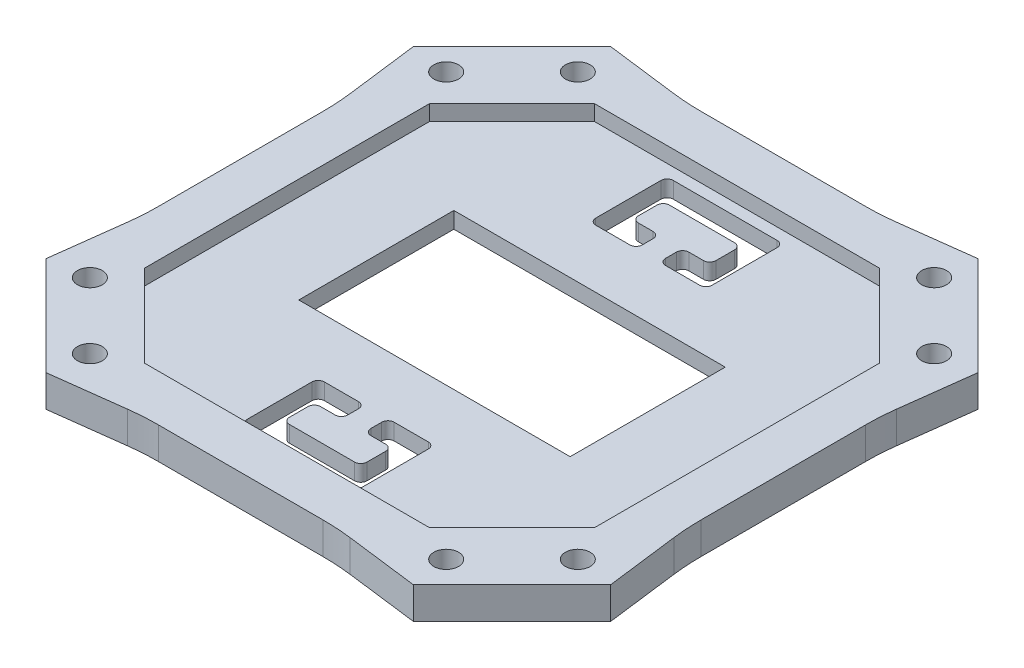
SolidWorks part; units mm, degrees
ref_plane "Front Plane" through (0, 0, 0) normal (0, 0, 1) x (1, 0, 0)
ref_plane "Top Plane" through (0, 0, 0) normal (0, 1, 0) x (1, 0, 0)
ref_plane "Right Plane" through (0, 0, 0) normal (1, 0, 0) x (0, 0, -1)
sketch "Sketch1" plane through (0, 0, 0) normal (0, 1, 0) x (1, 0, 0)
  line L0 (0, 0) -> (84.8528, 84.8528) construction
  line L1 (-35, 35) -> (35, 35) construction
  line L2 (-35, 35) -> (-35, -35) construction
  line L3 (-35, -35) -> (35, -35) construction
  line L4 (35, 35) -> (35, -35) construction
  line L5 (-35, 35) -> (35, -35) construction
  line L6 (-35, -35) -> (35, 35) construction
  line L7 (0, 35) -> (0, -35) construction
  line L8 (-12.5, 35) -> (12.5, 35)
  line L9 (35, 12.5) -> (35, -12.5)
  line L10 (12.5, -35) -> (-12.5, -35)
  line L11 (-35, -12.5) -> (-35, 12.5)
  line L12 (20.8564, 33.5843) -> (33.5843, 20.8564) construction
  line L13 (23.6848, 36.4127) -> (36.4127, 23.6848)
  line L14 (12.5, 35) -> (23.6848, 36.4127)
  line L15 (35, 12.5) -> (36.4127, 23.6848)
  line L16 (35, -12.5) -> (36.4127, -23.6848)
  line L17 (36.4127, -23.6848) -> (23.6848, -36.4127)
  line L18 (12.5, -35) -> (23.6848, -36.4127)
  line L19 (-12.5, -35) -> (-23.6848, -36.4127)
  line L20 (-23.6848, -36.4127) -> (-36.4127, -23.6848)
  line L21 (-35, -12.5) -> (-36.4127, -23.6848)
  line L22 (-35, 12.5) -> (-36.4127, 23.6848)
  line L23 (-36.4127, 23.6848) -> (-23.6848, 36.4127)
  line L24 (-12.5, 35) -> (-23.6848, 36.4127)
  circle A0 centre (22.9777, 31.463) radius 1.6
  circle A1 centre (31.463, 22.9777) radius 1.6
  circle A2 centre (31.463, -22.9777) radius 1.6
  circle A3 centre (22.9777, -31.463) radius 1.6
  circle A4 centre (-22.9777, -31.463) radius 1.6
  circle A5 centre (-31.463, -22.9777) radius 1.6
  circle A6 centre (-31.463, 22.9777) radius 1.6
  circle A7 centre (-22.9777, 31.463) radius 1.6
  point P0 (0, 0)
  point P21 (0, 0)
  point P54 (0, 0)
  dimension "D13" = 3.2
  dimension "D14" = 3.2
  dimension "D1" = 70
  dimension "D2" = 70
  dimension "D3" = 120
  dimension "D4" = 25
  dimension "D5" = 12.5
  dimension "D7" = 18
  dimension "D8" = 9
  dimension "D9" = 82
  dimension "D10" = 4
  dimension "D11" = 18
  dimension "D12" = 9
  dimension "D15" = 6
  dimension "D16" = 6
  dimension "D6" = 4
  dimension "D17" = 4
extrude "Boss-Extrude1" add sketch "Sketch1" along normal blind 4.1
sketch "Sketch2" plane through (0, 4.1, 0) normal (0, 1, 0) x (1, 0, 0)
  line L0 (0, 35) -> (0, 0)
  line L1 (12.5, 35) -> (-12.5, 35) construction
  line L2 (0, 0) -> (-35, 0)
  line L3 (-35, 12.5) -> (-35, -12.5) construction
  line L4 (-18.3696, 29) -> (18.3696, 29)
  line L5 (-4.7606, 29) -> (0, 29)
  line L6 (18.3696, 29) -> (29, 18.3696)
  line L7 (29, 18.3696) -> (29, -18.3696)
  line L8 (29, -18.3696) -> (18.3696, -29)
  line L9 (18.3696, -29) -> (-18.3696, -29)
  line L10 (-18.3696, -29) -> (-29, -18.3696)
  line L11 (-29, -18.3696) -> (-29, 18.3696)
  line L12 (-29, 18.3696) -> (-18.3696, 29)
  line L13 (-36.4127, -23.6848) -> (-23.6848, -36.4127) construction
  line L15 (-12.5, -35) -> (12.5, -35) construction
  line L16 (23.6848, -36.4127) -> (36.4127, -23.6848) construction
  line L17 (-23.6848, 36.4127) -> (-36.4127, 23.6848) construction
  line L18 (36.4127, 23.6848) -> (23.6848, 36.4127) construction
  line L19 (35, -12.5) -> (35, 12.5) construction
  dimension "D1" = 6
  dimension "D2" = 9
  dimension "D3" = 6
  dimension "D4" = 9
  dimension "D5" = 6
extrude "Cut-Extrude1" cut sketch "Sketch2" against normal blind 2 contours L12 L11 L2 L0 L4 | L11 L10 L9 L8 L7 L6 L4 L0 L2 region at (4.5703, 4.1, 4.5703) region at (-13.7109, 4.1, -13.7109)
sketch "Sketch3" plane through (0, 2.1, 0) normal (0, 1, 0) x (1, 0, 0)
  line L0 (0, 29) -> (0, 0) construction
  line L1 (-18.3696, 29) -> (18.3696, 29) construction
  line L2 (0, 0) -> (-29, 0) construction
  line L3 (-29, -18.3696) -> (-29, 18.3696) construction
  line L4 (-15, 4.6474) -> (-15, -4.6474)
  line L5 (-16.0136, -6.8956) -> (-24.0136, -13.964)
  line L6 (-29, -11.7158) -> (-29, 11.7158)
  line L7 (-24.0136, 13.964) -> (-16.0136, 6.8956)
  line L8 (-11.7158, 29) -> (11.7158, 29)
  line L9 (-6.8956, 16.0136) -> (-13.964, 24.0136)
  line L10 (4.6474, 15) -> (-4.6474, 15)
  line L11 (13.964, 24.0136) -> (6.8956, 16.0136)
  line L12 (29, 11.7158) -> (29, -11.7158)
  line L13 (16.0136, 6.8956) -> (24.0136, 13.964)
  line L14 (15, -4.6474) -> (15, 4.6474)
  line L15 (24.0136, -13.964) -> (16.0136, -6.8956)
  line L16 (11.7158, -29) -> (-11.7158, -29)
  line L17 (6.8956, -16.0136) -> (13.964, -24.0136)
  line L18 (-4.6474, -15) -> (4.6474, -15)
  line L19 (-13.964, -24.0136) -> (-6.8956, -16.0136)
  arc A0 (-15, 4.6474) -> (-16.0136, 6.8956) centre (-18, 4.6474) ccw
  arc A1 (-15, -4.6474) -> (-16.0136, -6.8956) centre (-18, -4.6474) cw
  arc A2 (-24.0136, -13.964) -> (-29, -11.7158) centre (-26, -11.7158) cw
  arc A3 (-29, 11.7158) -> (-24.0136, 13.964) centre (-26, 11.7158) cw
  arc A4 (11.7158, 29) -> (13.964, 24.0136) centre (11.7158, 26) cw
  arc A5 (-13.964, 24.0136) -> (-11.7158, 29) centre (-11.7158, 26) cw
  arc A6 (-4.6474, 15) -> (-6.8956, 16.0136) centre (-4.6474, 18) cw
  arc A7 (4.6474, 15) -> (6.8956, 16.0136) centre (4.6474, 18) ccw
  arc A8 (29, -11.7158) -> (24.0136, -13.964) centre (26, -11.7158) cw
  arc A9 (24.0136, 13.964) -> (29, 11.7158) centre (26, 11.7158) cw
  arc A10 (15, 4.6474) -> (16.0136, 6.8956) centre (18, 4.6474) cw
  arc A11 (15, -4.6474) -> (16.0136, -6.8956) centre (18, -4.6474) ccw
  arc A12 (-11.7158, -29) -> (-13.964, -24.0136) centre (-11.7158, -26) cw
  arc A13 (13.964, -24.0136) -> (11.7158, -29) centre (11.7158, -26) cw
  arc A14 (4.6474, -15) -> (6.8956, -16.0136) centre (4.6474, -18) cw
  arc A15 (-4.6474, -15) -> (-6.8956, -16.0136) centre (-4.6474, -18) ccw
  point P18 (-15, 6)
  point P21 (-15, -6)
  point P24 (-29, -18.3696)
  point P27 (-29, 18.3696)
  point P65 (0, 0)
  dimension "D3" = 3
  dimension "D1" = 15
  dimension "D2" = 12
  dimension "D4" = 4
extrude "Cut-Extrude2" [suppressed] cut sketch "Sketch3" against normal blind 1.5
sketch "Sketch4" plane through (0, 2.1, 0) normal (0, 1, 0) x (1, 0, 0)
  line L1 (0, 0) -> (15.25, 0) construction
  line L2 (0, 0) -> (0, 15.25) construction
  line L3 (0, 15.25) -> (15.25, 15.25) construction
  line L4 (15.25, 0) -> (15.25, 15.25) construction
  circle A0 centre (15.25, 15.25) radius 1.5
  dimension "D2" = 3
  dimension "D1" = 15.25
extrude "Cut-Extrude3" [suppressed] cut sketch "Sketch4" against normal through all
sketch "Sketch5" [suppressed] plane through (0, 2, 0) normal (0, 1, 0) x (1, 0, 0)
  circle A0 centre (15.25, 15.25) radius 4
  circle A1 centre (15.25, 15.25) radius 1.5 construction
  circle A2 centre (15.25, 15.25) radius 1.5
  dimension "D1" = 8
extrude "Boss-Extrude3" [suppressed] add sketch "Sketch5" along normal blind 1.5
ref_axis "Axis1" through (0, 4.2, 0) along (0, -1, 0)
pattern_circular "CirPattern1" [suppressed] count 4 over 360 about axis through (0, 4.2, 0) along (0, -1, 0) of bodies 106
fillet "Fillet1" [suppressed] radius 2
fillet "Fillet2" radius 30 8 edges at (-35, 2.05, 12.5) (-35, 2.05, -12.5) (-12.5, 2.05, -35) (12.5, 2.05, -35) (35, 2.05, -12.5) (35, 2.05, 12.5) (12.5, 2.05, 35) (-12.5, 2.05, 35)
sketch "Sketch6" plane through (0, 2.1, 0) normal (0, 1, 0) x (1, 0, 0)
  line L0 (0, 0) -> (0, 24.5268) construction
  line L1 (0, 0) -> (-22.3432, 0) construction
  line L2 (-1.5, 19.7) -> (-1.5, 18.3)
  line L3 (-6.7, 27.5) -> (6.7, 27.5)
  line L4 (-7.5, 26.7) -> (-7.5, 18.3)
  line L5 (-6.7, 17.5) -> (-2.3, 17.5)
  line L6 (7.5, 26.7) -> (7.5, 18.3)
  line L7 (-7.5, 27.5) -> (7.5, 17.5) construction
  line L8 (-7.5, 17.5) -> (7.5, 27.5) construction
  line L9 (-4.2, 24.5) -> (4.2, 24.5)
  line L10 (-5, 23.7) -> (-5, 21.3)
  line L11 (-4.2, 20.5) -> (-2.3, 20.5)
  line L12 (5, 23.7) -> (5, 21.3)
  line L13 (-5, 24.5) -> (5, 20.5) construction
  line L14 (-5, 20.5) -> (5, 24.5) construction
  line L15 (1.5, 19.7) -> (1.5, 18.3)
  line L16 (2.3, 20.5) -> (4.2, 20.5)
  line L17 (2.3, 17.5) -> (6.7, 17.5)
  line L18 (-1.5, -19.7) -> (-1.5, -18.3)
  line L19 (-4.2, -20.5) -> (-2.3, -20.5)
  line L20 (-5, -23.7) -> (-5, -21.3)
  line L21 (-4.2, -24.5) -> (4.2, -24.5)
  line L22 (5, -23.7) -> (5, -21.3)
  line L23 (2.3, -20.5) -> (4.2, -20.5)
  line L24 (1.5, -19.7) -> (1.5, -18.3)
  line L25 (2.3, -17.5) -> (6.7, -17.5)
  line L26 (7.5, -26.7) -> (7.5, -18.3)
  line L27 (-6.7, -27.5) -> (6.7, -27.5)
  line L28 (-7.5, -26.7) -> (-7.5, -18.3)
  line L29 (-6.7, -17.5) -> (-2.3, -17.5)
  arc A0 (-7.5, 18.3) -> (-6.7, 17.5) centre (-6.7, 18.3) ccw
  arc A1 (1.5, 19.7) -> (2.3, 20.5) centre (2.3, 19.7) cw
  arc A2 (-1.5, 19.7) -> (-2.3, 20.5) centre (-2.3, 19.7) ccw
  arc A3 (4.2, 24.5) -> (5, 23.7) centre (4.2, 23.7) cw
  arc A4 (-5, 21.3) -> (-4.2, 20.5) centre (-4.2, 21.3) ccw
  arc A5 (-4.2, 24.5) -> (-5, 23.7) centre (-4.2, 23.7) ccw
  arc A6 (4.2, 20.5) -> (5, 21.3) centre (4.2, 21.3) ccw
  arc A7 (6.7, 27.5) -> (7.5, 26.7) centre (6.7, 26.7) cw
  arc A8 (-6.7, 27.5) -> (-7.5, 26.7) centre (-6.7, 26.7) ccw
  arc A9 (6.7, 17.5) -> (7.5, 18.3) centre (6.7, 18.3) ccw
  arc A10 (1.5, 18.3) -> (2.3, 17.5) centre (2.3, 18.3) ccw
  arc A11 (-1.5, 18.3) -> (-2.3, 17.5) centre (-2.3, 18.3) cw
  arc A12 (-1.5, -18.3) -> (-2.3, -17.5) centre (-2.3, -18.3) ccw
  arc A13 (-1.5, -19.7) -> (-2.3, -20.5) centre (-2.3, -19.7) cw
  arc A14 (-5, -21.3) -> (-4.2, -20.5) centre (-4.2, -21.3) cw
  arc A15 (-4.2, -24.5) -> (-5, -23.7) centre (-4.2, -23.7) cw
  arc A16 (4.2, -24.5) -> (5, -23.7) centre (4.2, -23.7) ccw
  arc A17 (4.2, -20.5) -> (5, -21.3) centre (4.2, -21.3) cw
  arc A18 (1.5, -19.7) -> (2.3, -20.5) centre (2.3, -19.7) ccw
  arc A19 (1.5, -18.3) -> (2.3, -17.5) centre (2.3, -18.3) cw
  arc A20 (6.7, -17.5) -> (7.5, -18.3) centre (6.7, -18.3) cw
  arc A21 (6.7, -27.5) -> (7.5, -26.7) centre (6.7, -26.7) ccw
  arc A22 (-6.7, -27.5) -> (-7.5, -26.7) centre (-6.7, -26.7) cw
  arc A23 (-7.5, -18.3) -> (-6.7, -17.5) centre (-6.7, -18.3) cw
  point P3 (0, 22.5)
  point P9 (0, 22.5)
  point P14 (-7.5, 22.5)
  point P24 (1.5, 20.5)
  point P27 (-1.5, 20.5)
  point P51 (1.5, 17.5)
  point P54 (-1.5, 17.5)
  dimension "D7" = 0.8
  dimension "D8" = 0.8
  dimension "D1" = 17.5
  dimension "D2" = 10
  dimension "D3" = 15
  dimension "D4" = 2.5
  dimension "D5" = 3
  dimension "D6" = 6
extrude "Cut-Extrude4" cut sketch "Sketch6" against normal through all
sketch "Sketch7" plane through (0, 2.1, 0) normal (0, 1, 0) x (1, 0, 0)
  line L1 (-17.5, 10) -> (17.5, 10)
  line L2 (-17.5, 10) -> (-17.5, -10)
  line L3 (-17.5, -10) -> (17.5, -10)
  line L4 (17.5, 10) -> (17.5, -10)
  line L5 (-17.5, 10) -> (17.5, -10) construction
  line L6 (-17.5, -10) -> (17.5, 10) construction
  point P0 (0, 0)
  dimension "D1" = 20
  dimension "D2" = 35
extrude "Cut-Extrude5" cut sketch "Sketch7" against normal through all
